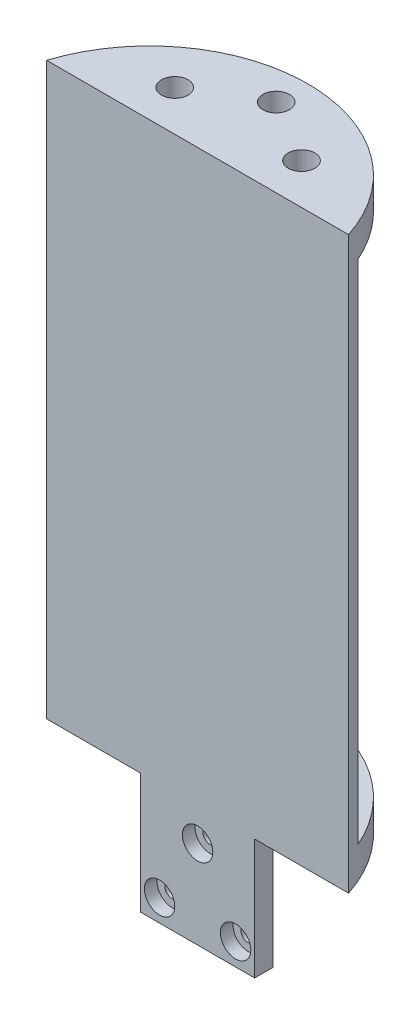
SolidWorks part; units mm, degrees
ref_plane "Front Plane" through (0, 0, 0) normal (0, 0, 1) x (1, 0, 0)
ref_plane "Top Plane" through (0, 0, 0) normal (0, 1, 0) x (1, 0, 0)
ref_plane "Right Plane" through (0, 0, 0) normal (1, 0, 0) x (0, 0, -1)
sketch "Sketch1" plane through (0, 0, 0) normal (0, 1, 0) x (1, 0, 0)
  line L1 (-30.2473, -9.652) -> (30.2473, -9.652)
  line L2 (-30.2473, -9.652) -> (-30.2473, 9.652)
  line L3 (-30.2473, 9.652) -> (30.2473, 9.652)
  line L4 (30.2473, -9.652) -> (30.2473, 9.652)
  line L5 (-30.2473, -9.652) -> (30.2473, 9.652) construction
  line L6 (-30.2473, 9.652) -> (30.2473, -9.652) construction
  circle A0 centre (0, 0) radius 31.75
  dimension "D1" = 63.5
  dimension "D2" = 19.304
extrude "Boss-Extrude1" add sketch "Sketch1" along normal mid plane 114.3 contours L3 A0 region at (0, 0, -18.8228)
sketch "Sketch2" plane through (0, -57.15, 0) normal (0, -1, 0) x (1, 0, 0)
  line L1 (-11.43, -9.525) -> (11.43, -9.525)
  line L2 (-11.43, -9.525) -> (-11.43, -13.335)
  line L3 (-11.43, -13.335) -> (11.43, -13.335)
  line L4 (12.7, -9.525) -> (-12.7, -9.525)
  line L5 (12.7, -14.605) -> (12.7, -9.525)
  line L6 (-12.7, -14.605) -> (12.7, -14.605)
  line L7 (-12.7, -9.525) -> (-12.7, -14.605)
  line L8 (12.7, -9.525) -> (-12.7, -9.525)
  line L9 (12.7, -14.605) -> (12.7, -9.525)
  line L10 (-12.7, -14.605) -> (12.7, -14.605)
  line L11 (-12.7, -9.525) -> (-12.7, -14.605)
  line L12 (11.43, -9.525) -> (11.43, -13.335)
  line M5 (30.2473, -9.652) -> (-30.2473, -9.652)
  dimension "D2" = 1.27
  dimension "D3" = 1.27
  dimension "D4" = 1.27
  dimension "D1" = 0
extrude "Boss-Extrude2" add sketch "Sketch2" along normal blind 24.13 contours L12 L2 L3 M5 region at (0, -57.15, -11.4935)
sketch "Sketch8" plane through (0, 57.15, 0) normal (0, 1, 0) x (1, 0, 0)
  line L0 (0, 25.4) -> (-12.7, 17.78) construction
  line L1 (-12.7, 17.78) -> (12.7, 17.78) construction
  line L2 (12.7, 17.78) -> (0, 25.4) construction
  circle A0 centre (0, 25.4) radius 2.667
  circle A1 centre (-12.7, 17.78) radius 2.667
  circle A2 centre (12.7, 17.78) radius 2.667
  dimension "D4" = 5.334
  dimension "D5" = 5.334
  dimension "D6" = 5.334
  dimension "D1" = 25.4
  dimension "D2" = 25.4
  dimension "D3" = 7.62
extrude "Cut-Extrude3" cut sketch "Sketch8" against normal blind 5.08 contours A0 | A1 | A2 region at (0, 57.15, -25.4) region at (-12.7, 57.15, -17.78) region at (12.7, 57.15, -17.78)
sketch "Sketch3" plane through (0, 0, -9.652) normal (0, 0, 1) x (1, 0, 0)
  line L0 (11.43, -81.28) -> (-11.43, -81.28) construction
  line L3 (0, -63.6412) -> (-7.62, -76.8395) construction
  line L4 (-7.62, -76.8395) -> (7.62, -76.8395) construction
  line L5 (7.62, -76.8395) -> (0, -63.6412) construction
  line L6 (11.43, -81.28) -> (11.43, -57.15) construction
  circle A0 centre (0, -63.6412) radius 3.048
  circle A1 centre (-7.62, -76.8395) radius 3.048
  circle A2 centre (7.62, -76.8395) radius 3.048
  point P2 (0, 0)
  dimension "D2" = 6.096
  dimension "D3" = 6.096
  dimension "D4" = 6.096
  dimension "D1" = 15.24
  dimension "D5" = 4.4405
  dimension "D6" = 11.43
extrude "Cut-Extrude1" cut sketch "Sketch3" against normal blind 2.54
hole_wizard "Ø3.0mm Dowel Hole1" positions "Sketch4" profile "Sketch5" hole size "Ø3.0" standard "ANSI Metric" end condition through all
sketch "Sketch4" plane through (0, 0, -9.652) normal (0, 0, 1) x (1, 0, 0)
  point P0 (0, -63.6412)
  point P3 (7.62, -76.8395)
  point P6 (-7.62, -76.8395)
sketch "Sketch5" plane through (0, -63.6412, -9.652) normal (1, 0, 0) x (0, -1, 0)
  line L0 (0, 0) -> (0, 22.098)
  line L1 (0, 22.098) -> (1.5, 22.098)
  line L2 (1.5, 22.098) -> (1.5, 0)
  line L5 (1.5, 0) -> (0, 0)
  line L11 (0, -6.35) -> (0, 107.95) construction
  dimension "Thru Hole Dia." = 3
  dimension "Thru Hole Depth" = 22.098
ref_plane "Plane1" through (0, 0, -31.75) normal (0, 0, -1) x (-1, 0, 0)
sketch "Sketch6" plane through (0, 0, -31.75) normal (0, 0, -1) x (-1, 0, 0)
  line L0 (-30.2473, 57.15) -> (-30.2473, -57.15) construction
  line L1 (-30.2473, 50.8) -> (30.2473, 50.8)
  line L2 (-30.2473, 50.8) -> (-30.2473, -50.8)
  line L3 (-30.2473, -50.8) -> (30.2473, -50.8)
  line L4 (30.2473, 50.8) -> (30.2473, -50.8)
  line L5 (30.2473, 57.15) -> (30.2473, -57.15) construction
  line L6 (-30.2473, -57.15) -> (30.2473, -57.15) construction
  line L7 (30.2473, 57.15) -> (-30.2473, 57.15) construction
  dimension "D1" = 6.35
  dimension "D2" = 6.35
extrude "Cut-Extrude2" cut sketch "Sketch6" against normal blind 19.05
sketch "Sketch7" plane through (0, 50.8, 0) normal (0, -1, 0) x (1, 0, 0)
  line L0 (3.175, -31.5909) -> (-3.175, -31.5909)
  line L1 (-29.0994, -12.7) -> (29.0994, -12.7) construction
  line L3 (29.0994, -12.7) -> (-29.0994, -12.7)
  line L4 (29.0994, -12.7) -> (-29.0994, -12.7)
  line L5 (3.175, -31.5909) -> (-3.175, -31.5909)
  line L6 (3.175, -31.5909) -> (3.175, -12.7)
  line L7 (3.175, -12.7) -> (-3.175, -12.7)
  line L8 (-3.175, -31.5909) -> (-3.175, -12.7)
  arc A0 (-29.0994, -12.7) -> (29.0994, -12.7) centre (0, 0) ccw construction
  arc A1 (-29.0994, -12.7) -> (-3.175, -31.5909) centre (0, 0) ccw
  arc A2 (-29.0994, -12.7) -> (29.0994, -12.7) centre (0, 0) ccw
  arc A3 (3.175, -31.5909) -> (29.0994, -12.7) centre (0, 0) ccw
  arc M3 (-29.0994, -12.7) -> (29.0994, -12.7) centre (0, 0) ccw
  dimension "D1" = 6.35
  dimension "D2" = 0
extrude "Boss-Extrude3" add sketch "Sketch7" along normal up to surface (101.6 mm away) contours L0 M3 | L8 L0 L6 L4 region at (0, 50.8, -31.6545) region at (0, 50.8, -22.1454) up to face at (0, -50.8, -22.225)
fillet "Fillet1" radius 2.54 6 edges at (3.175, 0, -12.7) (-3.175, 0, -12.7) (-3.175, -50.8, -22.1454) (3.175, -50.8, -22.1454) (-3.175, 50.8, -22.1454) (3.175, 50.8, -22.1454)
